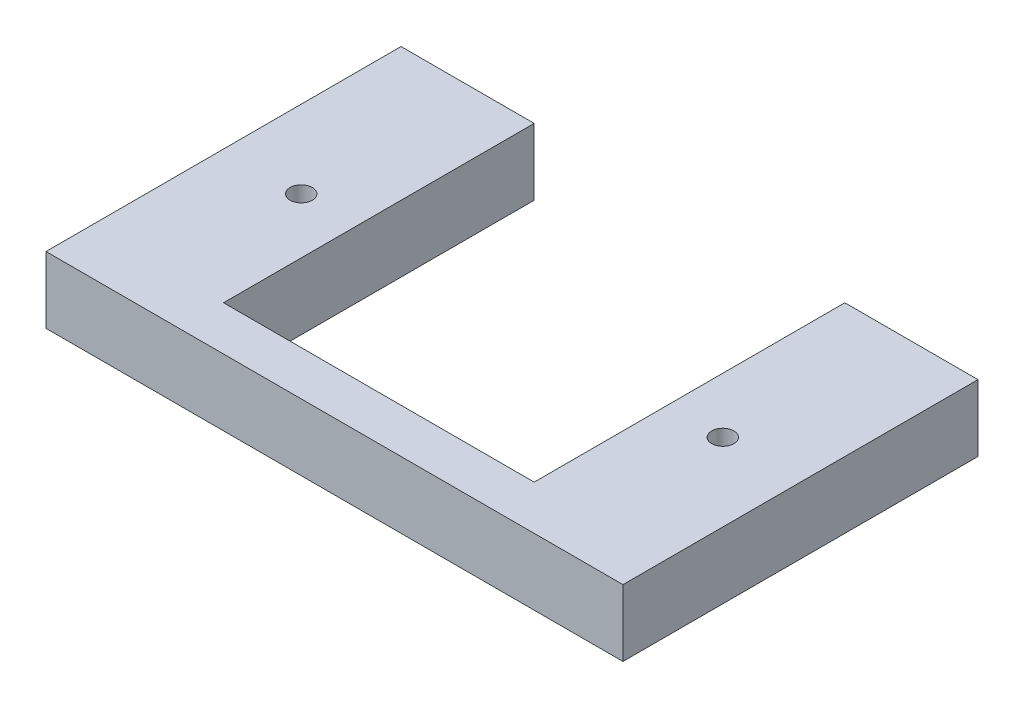
SolidWorks part; units mm, degrees
material "6061 Alloy"
ref_plane "Front Plane" through (0, 0, 0) normal (0, 0, 1) x (1, 0, 0)
ref_plane "Top Plane" through (0, 0, 0) normal (0, 1, 0) x (1, 0, 0)
ref_plane "Right Plane" through (0, 0, 0) normal (1, 0, 0) x (0, 0, -1)
sketch "Sketch1" plane through (0, 0, 0) normal (0, 1, 0) x (1, 0, 0)
  line L1 (-82.55, -50.8) -> (82.55, -50.8)
  line L2 (-82.55, -50.8) -> (-82.55, 50.8)
  line L3 (-82.55, 50.8) -> (82.55, 50.8)
  line L4 (82.55, -50.8) -> (82.55, 50.8)
  line L5 (-82.55, -50.8) -> (82.55, 50.8) construction
  line L6 (-82.55, 50.8) -> (82.55, -50.8) construction
  point P0 (0, 0)
  dimension "D1" = 165.1
  dimension "D2" = 101.6
extrude "Boss-Extrude1" add sketch "Sketch1" along normal blind 19.05
sketch "Sketch2" plane through (0, 19.05, 0) normal (0, 1, 0) x (1, 0, 0)
  line L0 (82.55, 50.8) -> (-82.55, 50.8) construction
  line L1 (-44.45, 50.8) -> (44.45, 50.8)
  line L2 (-44.45, 50.8) -> (-44.45, -38.1)
  line L3 (-44.45, -38.1) -> (44.45, -38.1)
  line L4 (44.45, 50.8) -> (44.45, -38.1)
  line L5 (-82.55, 50.8) -> (-82.55, -50.8) construction
  line L6 (82.55, -50.8) -> (82.55, 50.8) construction
  line L7 (-82.55, -50.8) -> (82.55, -50.8) construction
  dimension "D1" = 38.1
  dimension "D2" = 38.1
  dimension "D3" = 12.7
extrude "Cut-Extrude1" cut sketch "Sketch2" against normal through all
sketch "Sketch3" plane through (0, 19.05, 0) normal (0, 1, 0) x (1, 0, 0)
  line L0 (-44.45, 50.8) -> (-82.55, 50.8) construction
  line L1 (82.55, 50.8) -> (44.45, 50.8) construction
  circle A0 centre (-60.325, 0) radius 3.175
  circle A1 centre (60.325, 0) radius 3.175
  dimension "D1" = 6.35
  dimension "D2" = 6.35
  dimension "D3" = 120.65
  dimension "D4" = 60.325
  dimension "D5" = 50.8
  dimension "D6" = 50.8
extrude "Cut-Extrude2" cut sketch "Sketch3" against normal blind 15.875
